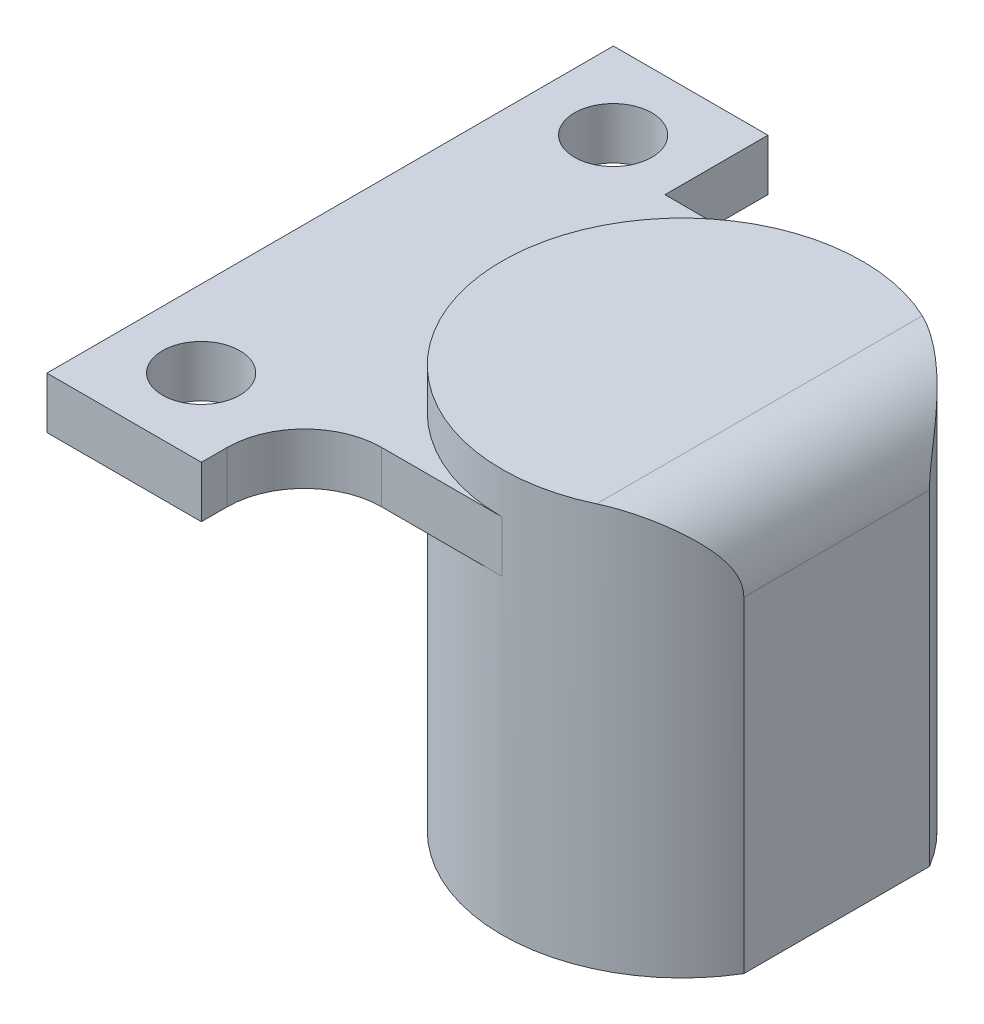
SolidWorks part; units mm, degrees
material "Copper"
ref_plane "Front Plane" through (0, 0, 0) normal (0, 0, 1) x (1, 0, 0)
ref_plane "Top Plane" through (0, 0, 0) normal (0, 1, 0) x (1, 0, 0)
ref_plane "Right Plane" through (0, 0, 0) normal (1, 0, 0) x (0, 0, -1)
sketch "Sketch1" plane through (0, 0, 0) normal (0, 1, 0) x (1, 0, 0)
  circle A0 centre (0, 0) radius 5.2
  circle A1 centre (0, 0) radius 7
  dimension "D1" = 10.4
  dimension "D2" = 14
extrude "Boss-Extrude1" add sketch "Sketch1" along normal blind 15.66
sketch "Sketch2" plane through (0, 15.66, 0) normal (0, 1, 0) x (1, 0, 0)
  line L0 (0, 0) -> (-6.5789, 0) construction
  line L1 (0, 5.2) -> (0, 7)
  line L2 (-13.67, -7) -> (0, -7)
  line L3 (-13.67, -7) -> (-13.67, 7)
  line L4 (-13.67, 7) -> (0, 7)
  line L5 (0, -7) -> (0, -5.2)
  line L6 (-13.67, -7) -> (0, 7) construction
  line L7 (-13.67, 7) -> (0, -7) construction
  line L8 (-7.67, 7) -> (-7.67, 11)
  line L9 (-13.67, -7) -> (-7.67, -7)
  line L10 (-13.67, -7) -> (-13.67, -11)
  line L11 (-13.67, -11) -> (-7.67, -11)
  line L12 (-7.67, -7) -> (-7.67, -11)
  line L13 (-13.67, 11) -> (-7.67, 11)
  line L14 (-13.67, 7) -> (-13.67, 11)
  line L15 (-13.67, 7) -> (-7.67, 7)
  circle A0 centre (0, 0) radius 7 construction
  circle A1 centre (0, 0) radius 5.2 construction
  arc A2 (0, 5.2) -> (0, -5.2) centre (0, 0) ccw
  point P3 (-6.835, 0)
  circle M6 centre (0, 0) radius 7
  dimension "D1" = 4
  dimension "D2" = 13.67
  dimension "D3" = 6
extrude "Boss-Extrude2" add sketch "Sketch2" against normal blind 3.6 contours L12 L2 L10 L11 | L4 L3 L2 M6 | L15 L8 L13 L14 region at (-9.4345, 15.66, 0) region at (-10.67, 15.66, 9)
extrude "Cut-Extrude2" cut sketch "Sketch2<3>" against normal blind 1.6 contours L4 L3 L2 M6 | L14 L4 L8 L13 | L12 L2 L10 L11 region at (-9.4345, 15.66, 0) region at (-10.67, 15.66, -9) region at (-10.67, 15.66, 9)
sketch "Sketch2<3>" plane through (0, 15.66, 0) normal (0, 1, 0) x (1, 0, 0) same geometry as "Sketch2"
sketch "Sketch4" plane through (0, 12.06, 0) normal (0, -1, 0) x (1, 0, 0)
  line L0 (-13.67, 8) -> (-7.899, 8) construction
  line L2 (-13.67, -11) -> (-13.67, 11) construction
  line L3 (0, 0) -> (-21.2142, 0) construction
  line L4 (-13.67, 11) -> (-7.67, 11) construction
  circle A0 centre (-10.68, 8) radius 1.5
  circle A1 centre (-10.68, -8) radius 1.5
  dimension "D1" = 3
  dimension "D2" = 2.99
  dimension "D3" = 3
extrude "Cut-Extrude1" cut sketch "Sketch4" against normal blind 10 contours A1 | A0 region at (-10.68, 12.06, -8)
fillet "Fillet7" radius 3 1 edges at (-7.67, 13.06, 7) type face fillet first side face at (-3.835, 13.06, 7) second side face at (-7.67, 13.06, 9)
sketch "Sketch5" plane through (0, 15.66, 0) normal (0, 1, 0) x (1, 0, 0)
  circle A0 centre (0, 0) radius 5.2 construction
  circle A1 centre (0, 0) radius 5.2
extrude "Boss-Extrude3" add sketch "Sketch5" against normal blind 1
sketch "Sketch6" plane through (0, 0, 0) normal (0, -1, 0) x (1, 0, 0)
  line L0 (6, -3.6056) -> (6, 3.6056)
  circle A0 centre (0, 0) radius 7 construction
  arc A3 (6, -3.6056) -> (6, 3.6056) centre (0, 0) ccw
  point P5 (7, 0)
  dimension "D1" = 1
extrude "Cut-Extrude3" cut sketch "Sketch6" along direction (0, 1, 0) on the side against the normal up to next
fillet "Fillet8" radius 3 1 edges at (6, 15.66, 0) type face fillet first side face at (6, 7.83, 0) second side face at (-0.5, 15.66, 0)
